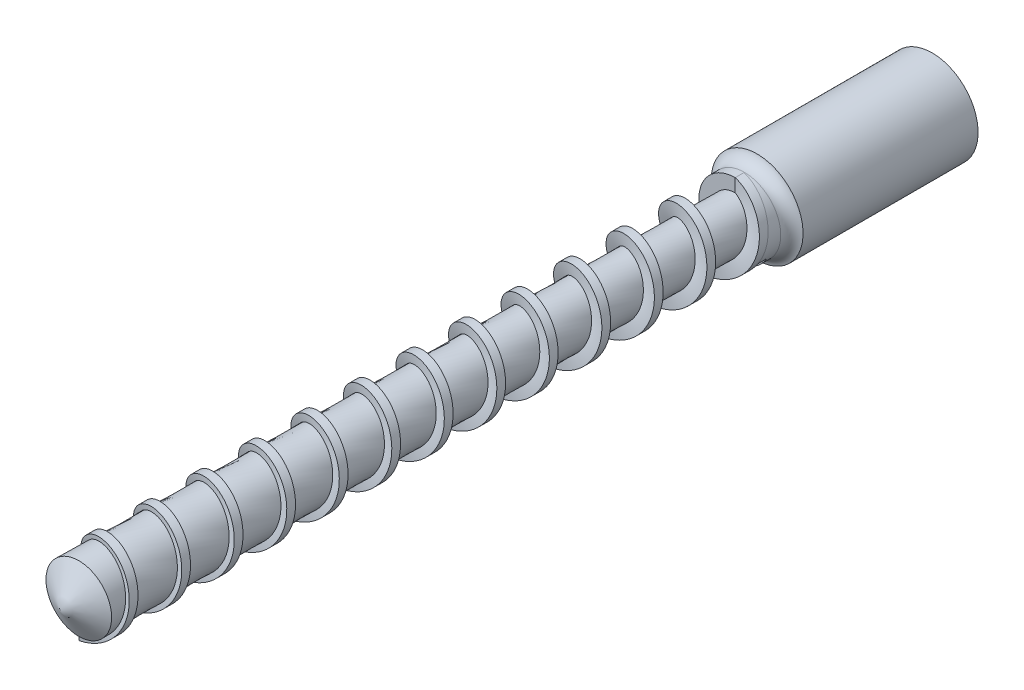
SolidWorks part; units mm, degrees
ref_plane "Front Plane" through (0, 0, 0) normal (0, 0, 1) x (1, 0, 0)
ref_plane "Top Plane" through (0, 0, 0) normal (0, 1, 0) x (1, 0, 0)
ref_plane "Right Plane" through (0, 0, 0) normal (1, 0, 0) x (0, 0, -1)
sketch "Sketch1" plane through (0, 0, 0) normal (0, 0, 1) x (1, 0, 0)
  circle A0 centre (0, 0) radius 8.3
  dimension "D1" = 16.6
curve "Helix/Spiral2" pitch 12 height 150 turns 12.5
sketch "Sketch2" plane through (0, 0, 0) normal (1, 0, 0) x (0, 0, -1)
  line L1 (0, 8.3) -> (2, 8.3)
  line L2 (0, 8.3) -> (0, 3.3)
  line L3 (0, 3.3) -> (2, 3.3)
  line L4 (2, 8.3) -> (2, 3.3)
  dimension "D1" = 2
  dimension "D2" = 5
sweep "Sweep1" add profiles "Sketch2" path "Helix/Spiral2"
sketch "Sketch4" plane through (0, 0, 0) normal (1, 0, 0) x (0, 0, -1)
  line L0 (10.8942, 0) -> (-170.3228, 0) construction
  line L1 (0, 5.3) -> (0, 8.3)
  line L2 (0, 8.3) -> (0, 3.3) construction
  line L3 (0, 8.3) -> (5, 8.3)
  line L4 (5, 8.3) -> (5, 10.5)
  line L5 (0, 5.3) -> (-150, 7.5)
  line L8 (-150, 7.5) -> (-154.3301, 0)
  line L9 (10, 0) -> (-154.3301, 0)
  line L10 (5, 10.5) -> (45, 10.5)
  line L11 (45, 10.5) -> (45, 0)
  line L14 (45, 0) -> (10, 0)
  dimension "D2" = 5
  dimension "D3" = 3
  dimension "D4" = 7.5
  dimension "D6" = 150
  dimension "D8" = 120
  dimension "D9" = 10.5
  dimension "D10" = 40
revolve "Revolve1" add sketch "Sketch4" angle 360 about L0
ref_plane "Plane2" through (0, 9, 0) normal (0, 1, 0) x (-1, 0, 0)
sketch "Sketch18" plane through (0, 0, 0) normal (0, 0, 1) x (1, 0, 0)
  line L0 (0, 0) -> (7.1865, 4.1527)
  line L1 (0, 0) -> (7.1896, -4.1473)
  line L2 (0, 0) -> (0, 5) construction
  arc A0 (7.1896, -4.1473) -> (7.1865, 4.1527) centre (0, 0) ccw
  circle A1 centre (0, 0) radius 8.3 construction
  dimension "D1" = 5
  dimension "D3" = 60
extrude "Boss-Extrude1" add sketch "Sketch18" along normal blind 2
sketch "Sketch19" plane through (0, 0, 0) normal (0, 0, 1) x (1, 0, 0)
  line L0 (0, 8.3) -> (0, 0)
  line L1 (0, 0) -> (5.3351, 6.3582)
  arc A0 (5.3351, 6.3582) -> (0, 8.3) centre (0, 0) ccw
  circle A1 centre (0, 0) radius 8.3 construction
  dimension "D1" = 40
sketch "Sketch20" plane through (0, 0, 0) normal (0, 0, 1) x (1, 0, 0)
  line L0 (0, 8.3) -> (0, 0)
  line L1 (0, 0) -> (2.1482, 8.0172)
  arc A0 (0, 8.3) -> (2.1482, 8.0172) centre (0, 0) cw
  circle A1 centre (0, 0) radius 8.3 construction
  dimension "D1" = 15
hole_wizard "Ø12.0 (12) Durchmesser Bohrung1" positions "Sketch22" profile "Sketch21" hole size "Ø12.0" standard "DIN"
sketch "Sketch22" plane through (0, 0, -45) normal (0, 0, -1) x (-1, 0, 0)
  circle A0 centre (0, 0) radius 10.5 construction
  point P0 (0, 0)
  dimension "D1" = 0
sketch "Sketch21" plane through (0, 0, -45) normal (1, 0, 0) x (0, 1, 0)
  line L0 (0, 0) -> (0, 33.6052)
  line L1 (0, 33.6052) -> (6, 30)
  line L2 (6, 30) -> (6, 0)
  line L5 (6, 0) -> (0, 0)
  line L10 (0, 33.6052) -> (-6, 30) construction
  line L11 (0, -6.35) -> (0, 107.95) construction
  dimension "Hole Dia." = 12
  dimension "Hole Depth" = 30
  dimension "Drill Angle" = 118
hole_wizard "M3 Tapped Hole1" [suppressed] positions "Sketch24" profile "Sketch23" tap size "M3" standard "DIN"
sketch "Sketch24" plane through (0, 9, 0) normal (0, 1, 0) x (-1, 0, 0)
  line L0 (9, -40) -> (9, -10) construction
  line L1 (-9, -40) -> (9, -40) construction
  point P1 (0, -30)
  dimension "D1" = 9
  dimension "D2" = 10
sketch "Sketch23" plane through (0, 9, -30) normal (1, 0, 0) x (0, 0, 1)
  line L0 (0, 0) -> (0, 4)
  line L1 (0, 4) -> (1.25, 4)
  line L2 (1.25, 4) -> (1.25, 0)
  line L5 (1.25, 0) -> (0, 0)
  line L11 (0, -6.35) -> (0, 107.95) construction
  dimension "Thru Tap Drill Dia." = 2.5
  dimension "Thru Tap Drill Depth" = 4
cosmetic thread "Hole Thread1" [suppressed] parameters "D2"=3
sketch "Skizze1" plane through (0, 0, -45) normal (0, 0, -1) x (-1, 0, 0)
  line L0 (0, 0) -> (0, 9.3018)
  line L1 (0, 7.8) -> (-2.05, 7.8)
  line L2 (0, 7.8) -> (2.05, 7.8)
  line L3 (2.05, 7.8) -> (2.05, 5.6389)
  line L4 (-2.05, 7.8) -> (-2.05, 5.6389)
  circle A0 centre (0, 0) radius 6 construction
  arc A1 (-2.05, 5.6389) -> (2.05, 5.6389) centre (0, 0) cw
  arc A2 (-2.05, 5.6389) -> (2.05, 5.6389) centre (0, 0) cw
  arc A3 (-2.05, 5.6389) -> (0, 6) centre (0, 0) cw
  dimension "D1" = 1.8
  dimension "D2" = 2.05
  dimension "D3" = 2.05
extrude "Schnitt-Linear austragen1" cut sketch "Skizze1" against normal blind 30 contours L4 A1 L3 L2 L1
fillet "Verrundung5" radius 3 1 edges at (-8.3, 0, -5)
